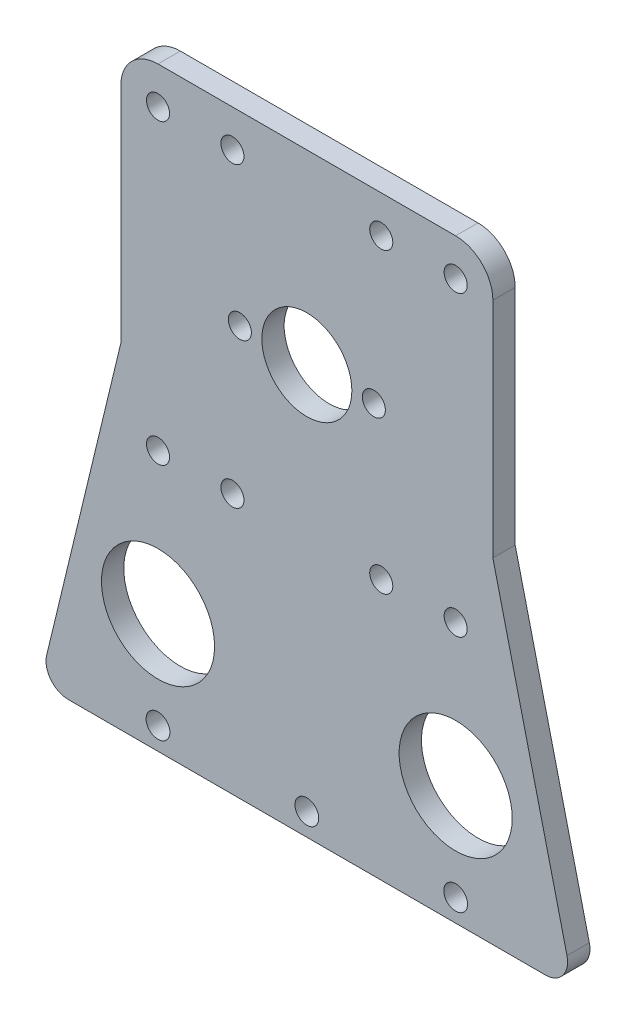
SolidWorks part; units mm, degrees
ref_plane "正面" through (0, 0, 0) normal (0, 0, 1) x (1, 0, 0)
ref_plane "平面" through (0, 0, 0) normal (0, 1, 0) x (1, 0, 0)
ref_plane "右側面" through (0, 0, 0) normal (1, 0, 0) x (0, 0, -1)
sketch "ｽｹｯﾁ1" plane through (0, 0, 0) normal (0, 0, 1) x (1, 0, 0)
  line L0 (0, 25) -> (0, -25) construction
  line L1 (-25, 25) -> (25, 25)
  line L2 (-25, 25) -> (-25, -25)
  line L3 (-25, -25) -> (25, -25)
  line L4 (25, 25) -> (25, -25)
  line L5 (-25, 25) -> (25, -25) construction
  line L6 (-25, -25) -> (25, 25) construction
  line L7 (0, 0) -> (-9, 0) construction
  circle A0 centre (-20, 20) radius 1.55
  circle A1 centre (20, 20) radius 1.55
  circle A2 centre (20, -20) radius 1.55
  circle A3 centre (-20, -20) radius 1.55
  circle A4 centre (0, 0) radius 6.05
  circle A5 centre (-9, 0) radius 1.55
  circle A6 centre (9, 0) radius 1.55
  point P0 (0, 0)
  dimension "D2" = 4
  dimension "D4" = 3.1
  dimension "D5" = 12.1
  dimension "D6" = 3.1
  dimension "D1" = 50
  dimension "D3" = 40
  dimension "D7" = 9
extrude "ﾎﾞｽ - 押し出し1" add sketch "ｽｹｯﾁ1" along normal blind 3
fillet "ﾌｨﾚｯﾄ1" radius 5 4 edges at (-25, -25, 1.5) (25, -25, 1.5) (25, 25, 1.5) (-25, 25, 1.5)
sketch "ｽｹｯﾁ2" plane through (0, 0, 3) normal (0, 0, 1) x (1, 0, 0)
  line L0 (0, 0) -> (0, 25) construction
  line L1 (20, 25) -> (-20, 25) construction
  line L2 (0, 20) -> (-10, 20) construction
  line L3 (-25, 0) -> (25, 0) construction
  line L4 (-25, 20) -> (-25, -20) construction
  line L5 (25, -20) -> (25, 20) construction
  circle A0 centre (-10, 20) radius 1.55
  circle A1 centre (10, 20) radius 1.55
  circle A2 centre (10, -20) radius 1.55
  circle A3 centre (-10, -20) radius 1.55
  dimension "D1" = 10
  dimension "D2" = 3.1
extrude "ｶｯﾄ - 押し出し1" cut sketch "ｽｹｯﾁ2" against normal through all
sketch "ｽｹｯﾁ3" plane through (0, 0, 3) normal (0, 0, 1) x (1, 0, 0)
  line L0 (25, -10) -> (34.9642, -51.2963)
  line L1 (25, -20) -> (25, 20) construction
  line L2 (35.8579, -55) -> (-35.8579, -55) construction
  line L3 (32.0479, -55) -> (-32.0479, -55)
  line L4 (-34.9642, -51.2963) -> (-25, -10)
  line L5 (-25, 20) -> (-25, -20) construction
  line L6 (-25, -10) -> (25, -10) construction
  line L10 (-25, 20) -> (-25, -20)
  line L11 (-20, -25) -> (20, -25)
  line L12 (25, -20) -> (25, 20)
  line L13 (20, 25) -> (-20, 25)
  line L14 (-25, -10) -> (-25, -20)
  line L15 (-20, -25) -> (20, -25)
  line L16 (25, -20) -> (25, -10)
  arc A0 (35.8579, -55) -> (42.9289, -37.9289) centre (35.8579, -45) ccw construction
  circle A1 centre (20, -52) radius 1.6 construction
  circle A2 centre (0, -52) radius 1.6 construction
  circle A3 centre (-20, -52) radius 1.6 construction
  circle A4 centre (20, -52) radius 1.6
  arc A5 (-25, -20) -> (-20, -25) centre (-20, -20) ccw
  arc A6 (20, -25) -> (25, -20) centre (20, -20) ccw
  arc A7 (25, 20) -> (20, 25) centre (20, 20) ccw
  arc A8 (-20, 25) -> (-25, 20) centre (-20, 20) ccw
  arc A9 (-25, -20) -> (-20, -25) centre (-20, -20) ccw
  arc A10 (20, -25) -> (25, -20) centre (20, -20) ccw
  circle A13 centre (0, -52) radius 1.6
  circle A14 centre (-20, -52) radius 1.6
  arc A15 (34.9642, -51.2963) -> (32.0479, -55) centre (32.0479, -52) cw
  arc A16 (-32.0479, -55) -> (-34.9642, -51.2963) centre (-32.0479, -52) cw
  circle A17 centre (20, -39) radius 5 construction
  circle A18 centre (-20, -39) radius 5 construction
  circle A19 centre (20, -39) radius 5 construction
  circle A20 centre (-20, -39) radius 5 construction
  circle A21 centre (-20, -39) radius 7.6
  circle A22 centre (20, -39) radius 7.6
  point P37 (35.8579, -55)
  point P40 (-35.8579, -55)
  dimension "D3" = 3
  dimension "D4" = 15.2
  dimension "D5" = 15.2
  dimension "D1" = 0
  dimension "D2" = 15
extrude "ﾎﾞｽ - 押し出し2" add sketch "ｽｹｯﾁ3" against normal up to surface (3 mm away) up to face at (-11.55, -20, 0)
